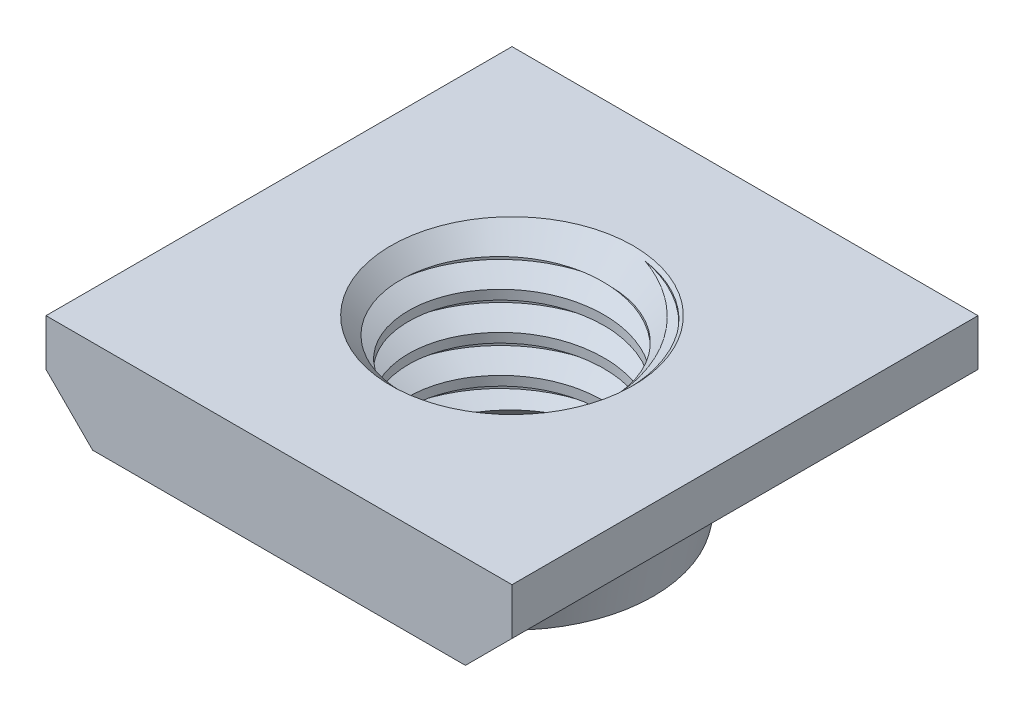
SolidWorks part; units mm, degrees
material "Stainless Steel (ferritic)"
ref_plane "Front Plane" through (0, 0, 0) normal (0, 0, 1) x (1, 0, 0)
ref_plane "Top Plane" through (0, 0, 0) normal (0, 1, 0) x (1, 0, 0)
ref_plane "Right Plane" through (0, 0, 0) normal (1, 0, 0) x (0, 0, -1)
sketch "Sketch1" plane through (0, 0, 0) normal (0, 0, 1) x (1, 0, 0)
  line L0 (-5, 1) -> (5, 1)
  line L1 (5, 1) -> (5, 0)
  line L2 (5, 0) -> (4, -1)
  line L3 (4, -1) -> (-4, -1)
  line L4 (-4, -1) -> (-5, 0)
  line L5 (-5, 0) -> (-5, 1)
  line L6 (-5, 0) -> (-5, -1) construction
  line L7 (-5, -1) -> (-4, -1) construction
  line L8 (4, -1) -> (5, -1) construction
  line L9 (5, -1) -> (5, 0) construction
  line L10 (-5, -1) -> (5, 1) construction
  line L11 (-5, 1) -> (5, -1) construction
  point P7 (-5, 0)
  dimension "D1" = 10
  dimension "D2" = 2
  dimension "D3" = 1
extrude "Boss-Extrude1" add sketch "Sketch1" along normal mid plane 10
sketch "Sketch2" plane through (0, 1, 0) normal (0, 1, 0) x (1, 0, 0)
  circle A0 centre (0, 0) radius 2.1
  dimension "D1" = 4.2
extrude "Cut-Extrude1" cut sketch "Sketch2" against normal through all
sketch "Sketch3" plane through (0, 0, 0) normal (1, 0, 0) x (0, 0, -1)
  line L0 (0, 1) -> (0, -2.3796) construction
  line L1 (-2.1, -1) -> (2.1, -1) construction
  line L2 (2.1, -1) -> (2.1, -2.7)
  line L3 (-5, -1) -> (5, -1) construction
  line L5 (2.1, -2.7) -> (3.033, -2.7)
  line L6 (3.033, -2.7) -> (3.3829, -1)
  line L7 (3.3829, -1) -> (2.1, -1)
  line L10 (-2.1, -1) -> (2.1, -1) construction
  point P1 (2.1, -2.7)
  point P8 (4.2233, -1)
  point P11 (2.1, -2.6788)
  point P12 (3.9405, -2.991)
  point P13 (0, 0)
  point P14 (2.0624, -2.2249)
  point P15 (0, 0)
  point P18 (0, 0)
  point P19 (2.1302, -1)
  dimension "D1" = 11.63
  dimension "D2" = 1.7
  dimension "D3" = 0.933
revolve "Revolve1" add sketch "Sketch3" angle 360 about L0
chamfer "Chamfer1" distance 0.5 angle 45 2 edges at (0, -2.7, 2.1) (0, 1, 2.1)
thread "Thread1" pitch 0.8 method cut profile "Thread Profile1" start angle 0, offset 1, length 5, pitch 0.8, diameter 4.2
ref_plane "Plane1" through (-2.1, 1.5, 0) normal (0, 0, 1) x (-1, 0, 0)
sketch "Thread Profile1" plane through (-2.1, 1.5, 0) normal (0, 0, 1) x (-1, 0, 0)
  line L0 (0, 0) -> (0, 0.8) construction
  line L1 (0, 0) -> (0.433, 0.25)
  line L2 (0.433, 0.25) -> (0.433, 0.35)
  line L3 (0.433, 0.35) -> (0, 0.6)
  line L4 (0.433, 0.3) -> (0, 0.3) construction
  line L11 (0, 0) -> (0, 0.6)
  point P2 (0, 0)
  dimension "Pitch" = 0.8
  dimension "Profile_Angle" = 60
  dimension "Profile_Land" = 0.1
  dimension "Profile_Height" = 0.433
